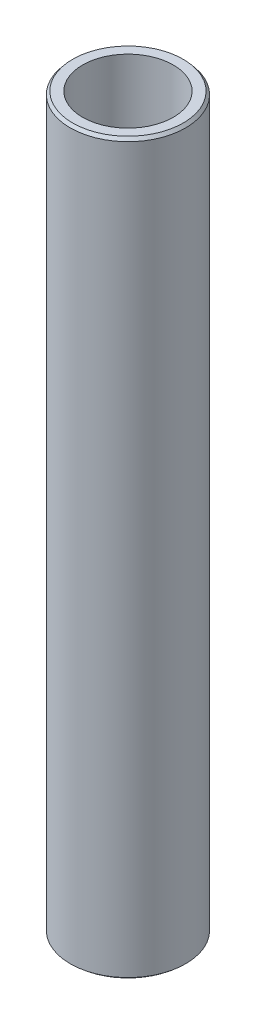
SolidWorks part; units mm, degrees
ref_plane "Front Plane" through (0, 0, 0) normal (0, 0, 1) x (1, 0, 0)
ref_plane "Top Plane" through (0, 0, 0) normal (0, 1, 0) x (1, 0, 0)
ref_plane "Right Plane" through (0, 0, 0) normal (1, 0, 0) x (0, 0, -1)
sketch "Sketch1" plane through (0, 0, 0) normal (0, 1, 0) x (1, 0, 0)
  circle A0 centre (0, 0) radius 47.5
  dimension "SHAFT_OD" = 95
extrude "Boss-Extrude1" add sketch "Sketch1" along normal blind 600
sketch "Sketch2" plane through (0, 0, 0) normal (0, 1, 0) x (1, 0, 0)
  circle A0 centre (0, 0) radius 37.3178
  dimension "BORE_D" = 74.6356
extrude "Cut-Extrude1" cut sketch "Sketch2" along normal through all
chamfer "Chamfer1" distance 2.4531 angle 39.649 2 edges at (0, 600, 47.5) (0, 0, 47.5) first distance on face at (0, 600, 47.5) first distance on face at (0, 0, 37.3178)
